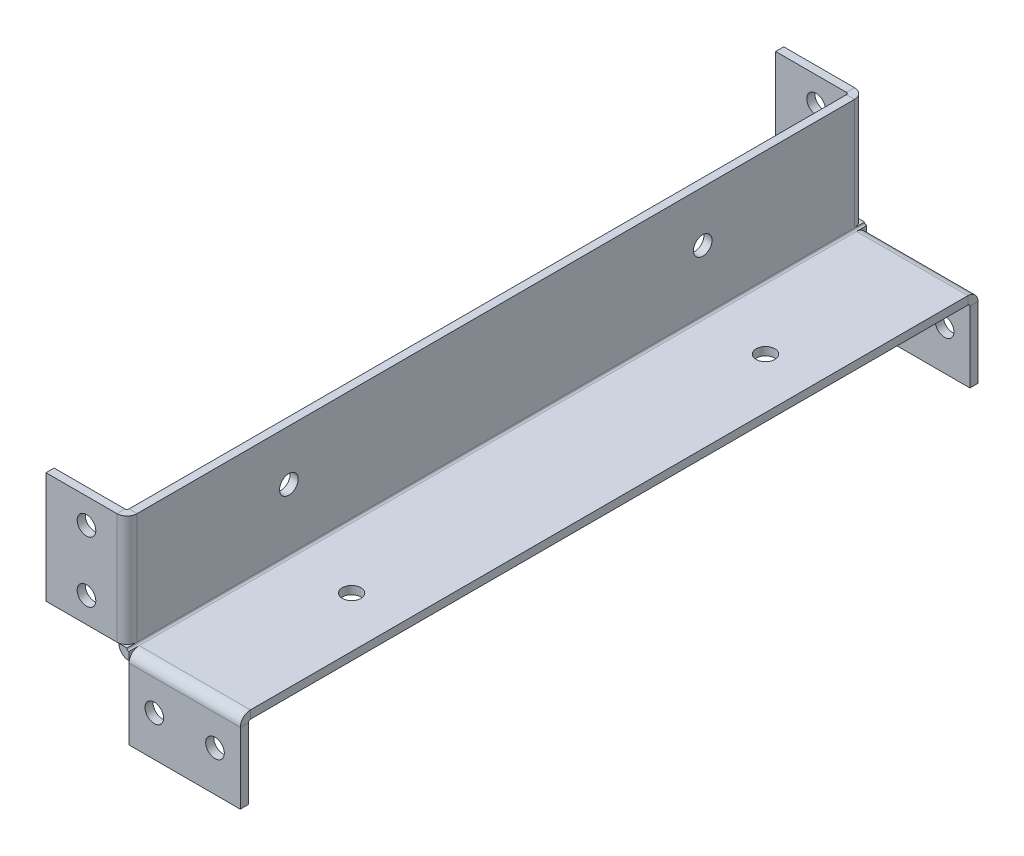
SolidWorks part; units mm, degrees
note: The reader was unsure of these and kept them because the rebuilt part matched: flange length of "Edge-Flange1", "Edge-Flange2".
ref_plane "Front Plane" through (0, 0, 0) normal (0, 0, 1) x (1, 0, 0)
ref_plane "Top Plane" through (0, 0, 0) normal (0, 1, 0) x (1, 0, 0)
ref_plane "Right Plane" through (0, 0, 0) normal (1, 0, 0) x (0, 0, -1)
sketch "Sketch1" plane through (0, 0, 0) normal (0, 1, 0) x (1, 0, 0)
  line L1 (30, 182.25) -> (-30, 182.25)
  line L2 (30, 182.25) -> (30, -182.25)
  line L3 (30, -182.25) -> (-30, -182.25)
  line L4 (-30, 182.25) -> (-30, -182.25)
  line L5 (30, 182.25) -> (-30, -182.25) construction
  line L6 (30, -182.25) -> (-30, 182.25) construction
  point P0 (0, 0)
  dimension "D1" = 60
  dimension "D2" = 364.5
sheet metal parameters "Sheet-Metal1" thickness 4 parameters "D1"=1
base flange "Base-Flange1" sketch "Sketch1" thickness 4 reverse thickness direction yes parameters "D1"=1
edge flange "Edge-Flange1" sketch "Sketch5" flange angle 90 flange length 60 flange position material inside bend radius 1 thickness 4 parameters "D6"=10
sketch "Sketch5" plane through (-30, 4, 0) normal (-1, 0, 0) x (0, 0, 1)
  line L2 (-182.25, 0) -> (-182.25, 56)
  line L3 (-182.25, 56) -> (182.25, 56)
  line L4 (182.25, 56) -> (182.25, 0)
  line L5 (-182.25, 0) -> (182.25, 0) construction
  line L6 (-182.25, 0) -> (182.25, 0)
bend "EdgeBend1" bend radius 1 bend angle 90 parameters "D5"=1
edge flange "Edge-Flange2" sketch "Sketch14" flange profiles "Sketch14", "Sketch15", "Sketch16", "Sketch17" flange angle 90 flange length 40 flange position material inside bend radius 1 thickness 4 relief none parameters "D6"=10, "D8"=0.5
sketch "Sketch14" plane through (-30, 0, 182.25) normal (0, 0, -1) x (0, -1, 0)
  line L1 (-5, 0) -> (-60, 0) construction
  line L2 (-60, 0) -> (-60, 36)
  line L3 (-60, 36) -> (-5, 36)
  line L4 (-5, 36) -> (-5, 0)
  line L5 (-5, 0) -> (-60, 0)
sketch "Sketch15" plane through (0, 0, 182.25) normal (0, 0, -1) x (1, 0, 0)
  line L0 (30, 0) -> (-25, 0) construction
  line L1 (30, 0) -> (-25, 0)
  line L2 (30, 0) -> (30, 36)
  line L3 (30, 36) -> (-25, 36)
  line L4 (-25, 36) -> (-25, 0)
sketch "Sketch16" plane through (-30, 0, -182.25) normal (0, 0, 1) x (0, 1, 0)
  line L0 (60, 0) -> (5, 0) construction
  line L1 (60, 0) -> (5, 0)
  line L2 (60, 0) -> (60, 36)
  line L3 (60, 36) -> (5, 36)
  line L4 (5, 36) -> (5, 0)
sketch "Sketch17" plane through (0, 0, -182.25) normal (0, 0, 1) x (-1, 0, 0)
  line L0 (25, 0) -> (-30, 0) construction
  line L1 (25, 0) -> (-30, 0)
  line L2 (25, 0) -> (25, 36)
  line L3 (25, 36) -> (-30, 36)
  line L4 (-30, 36) -> (-30, 0)
bend "EdgeBend2" bend radius 1 bend angle 90 parameters "D5"=2
bend "EdgeBend3" bend radius 1 bend angle 90 parameters "D5"=3
bend "EdgeBend4" bend radius 1 bend angle 90 parameters "D5"=4
bend "EdgeBend5" bend radius 1 bend angle 90 parameters "D5"=5
sketch "Sketch18" plane through (0, 0, 182.25) normal (0, 0, 1) x (1, 0, 0)
  line L0 (-25, 4) -> (30, 4) construction
  line L1 (-26, 60) -> (-26, 5) construction
  line L2 (-66, 60) -> (-31, 60) construction
  line L3 (30, -1) -> (30, -36) construction
  circle A0 centre (-46, 47.5) radius 4.6
  circle A1 centre (-46, 17.5) radius 4.6
  circle A2 centre (-12.5, -16) radius 4.6
  circle A3 centre (17.5, -16) radius 4.6
  dimension "D7" = 9.2
  dimension "D1" = 30
  dimension "D2" = 30
  dimension "D3" = 20
  dimension "D4" = 20
  dimension "D5" = 12.5
  dimension "D6" = 12.5
extrude "Extrude1" cut sketch "Sketch18" against normal through all normal cut yes
sketch "Sketch19" plane through (-26, 0, 0) normal (1, 0, 0) x (0, 0, -1)
  line L0 (-177.25, 60) -> (177.25, 60) construction
  line L1 (-182.25, 5) -> (-182.25, 60) construction
  line L2 (182.25, 5) -> (182.25, 60) construction
  circle A0 centre (-102.25, 35) radius 4.6
  circle A1 centre (102.25, 35) radius 4.6
  dimension "D4" = 9.2
  dimension "D1" = 25
  dimension "D2" = 80
  dimension "D3" = 80
extrude "Extrude2" cut sketch "Sketch19" against normal blind 4 normal cut yes
sketch "Sketch20" plane through (0, 4, 0) normal (0, 1, 0) x (1, 0, 0)
  line L0 (30, -177.25) -> (30, 177.25) construction
  line L1 (-25, -182.25) -> (30, -182.25) construction
  line L2 (30, 182.25) -> (-25, 182.25) construction
  circle A0 centre (5, 102.25) radius 4.6
  circle A1 centre (5, -102.25) radius 4.6
  dimension "D2" = 9.2
  dimension "D1" = 25
  dimension "D3" = 80
  dimension "D4" = 80
extrude "Extrude3" cut sketch "Sketch20" against normal blind 4 normal cut yes
flat pattern "Flat-Pattern1" [suppressed]
sketch "Bend-Lines1" plane through (0, 4, 0) normal (0, 1, 0) x (-1, 0, 0)
  line L0 (25, -199.4012) -> (-30, -199.4012) construction
  line L1 (82.8023, -199.4012) -> (27.8023, -199.4012) construction
  line L2 (-30, 199.4012) -> (25, 199.4012) construction
  line L3 (27.8023, 199.4012) -> (82.8023, 199.4012) construction
  line L4 (26.4012, -203) -> (26.4012, 203) construction
  line L5 (25, -199.4012) -> (-30, -199.4012) construction
  line L6 (82.8023, -199.4012) -> (27.8023, -199.4012) construction
  line L7 (-30, 199.4012) -> (25, 199.4012) construction
  line L8 (27.8023, 199.4012) -> (82.8023, 199.4012) construction
  line L9 (26.4012, -203) -> (26.4012, 203) construction
sketch3d "Bounding-Box1" [suppressed]
  line L0 (52.8023, 32.8023, 0) -> (52.8023, -438.8023, 0) construction
  line L1 (-60, 32.8023, 0) -> (-60, -438.8023, 0) construction
  line L2 (52.8023, 32.8023, 0) -> (-60, 32.8023, 0) construction
  line L3 (52.8023, -438.8023, 0) -> (-60, -438.8023, 0) construction
bend of the flat pattern "Flatten-<EdgeBend1>1"
bend of the flat pattern "Flatten-<EdgeBend2>1"
bend of the flat pattern "Flatten-<EdgeBend3>1"
bend of the flat pattern "Flatten-<EdgeBend4>1"
bend of the flat pattern "Flatten-<EdgeBend5>1"
